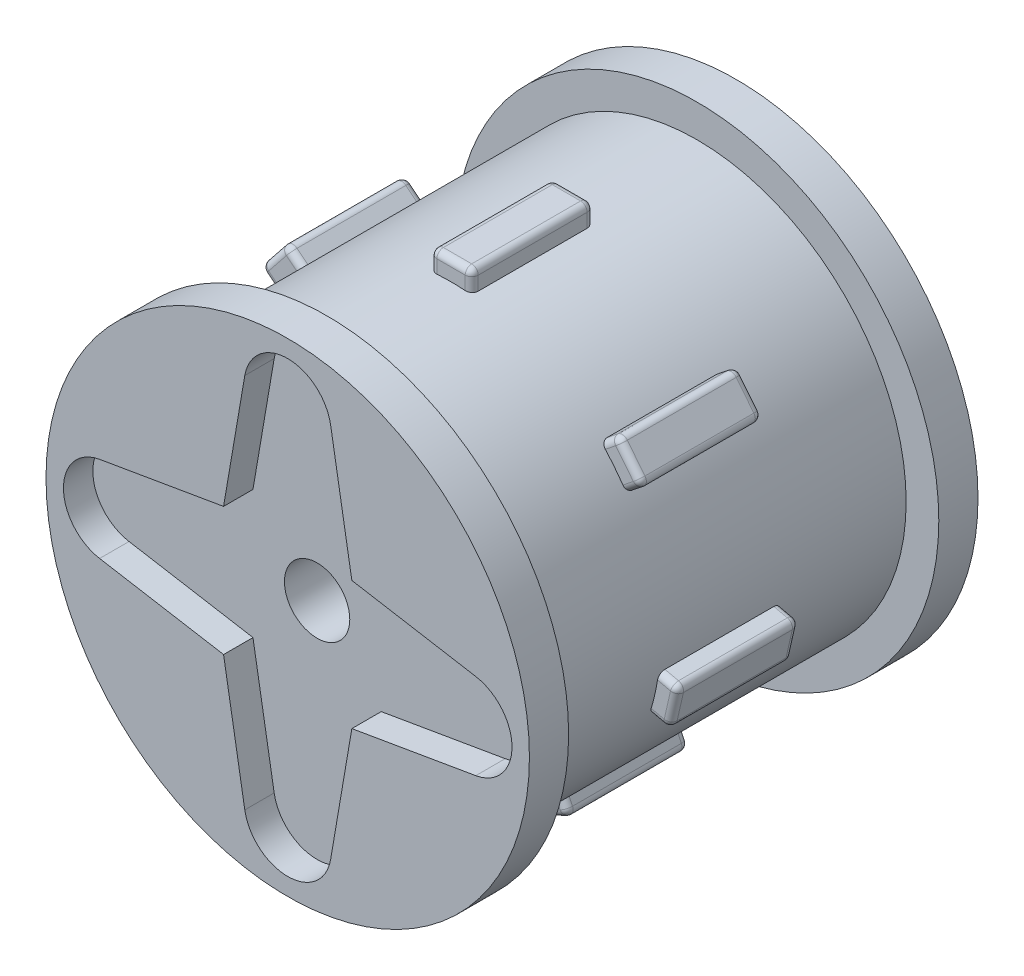
SolidWorks part; units mm, degrees
ref_plane "Ebene vorne" through (0, 0, 0) normal (0, 0, 1) x (1, 0, 0)
ref_plane "Ebene oben" through (0, 0, 0) normal (0, 1, 0) x (1, 0, 0)
ref_plane "Ebene rechts" through (0, 0, 0) normal (1, 0, 0) x (0, 0, -1)
sketch "Skizze1" plane through (0, 0, 0) normal (0, 0, 1) x (1, 0, 0)
  circle A0 centre (0, 0) radius 9.6
  dimension "D1" = 19.2
extrude "Aufsatz-Linear austragen1" add sketch "Skizze1" along normal blind 10.3 and the other way blind 10.3
ref_axis "Rotationsachse" through (0, 0, -10.3) along (0, 0, 1)
sketch "Skizze2" plane through (0, 0, 10.3) normal (0, 0, 1) x (1, 0, 0)
  circle A0 centre (0, 0) radius 11.1
  dimension "D1" = 22.2
extrude "Aufsatz-Linear austragen2" add sketch "Skizze2" against normal blind 1.8
sketch "Skizze3" plane through (0, 0, -10.3) normal (0, 0, -1) x (-1, 0, 0)
  circle A0 centre (0, 0) radius 11.1
  dimension "D1" = 22.2
extrude "Aufsatz-Linear austragen3" add sketch "Skizze3" against normal blind 1.8
sketch "Skizze4" plane through (0, 0, 10.3) normal (0, 0, 1) x (1, 0, 0)
  line L0 (-3.3513, 0.5735) -> (-1.9713, 8.6373)
  line L1 (3.3513, 0.5735) -> (1.9713, 8.6373)
  circle A0 centre (0, 0) radius 3.4
  circle A1 centre (0, 8.3) radius 2
  dimension "D1" = 6.8
  dimension "D3" = 4
  dimension "D2" = 8.3
extrude "Schnitt-Linear austragen1" cut sketch "Skizze4" against normal blind 1.35 contours A1 | A1 L0 A0 L1 | A0 region at (0, 4.7309, 10.3) region at (0, 0, 10.3) region at (0, 8.3, 10.3)
pattern_circular "Kreismuster1" count 4 over 360 about axis through (0, 0, -10.3) along (0, 0, 1) of "Schnitt-Linear austragen1"
sketch "Skizze8" plane through (0, 0, 0) normal (1, 0, 0) x (0, 0, -1)
  line L0 (10.3, 0) -> (10.3, 8)
  line L1 (10.3, -11.1) -> (10.3, 11.1) construction
  line L2 (10.3, 8) -> (8.5, 8)
  line L3 (8.5, 11.1) -> (8.5, -11.1) construction
  line L4 (8.5, 8) -> (-6.45, 3.5)
  line L6 (-6.45, 3.5) -> (-6.45, 0)
  line L7 (-6.45, 0) -> (10.3, 0)
  point P4 (-6.45, 0)
  dimension "D1" = 8
  dimension "D2" = 3.5
  dimension "D3" = 16.75
revolve "Schnitt-Rotation1" cut sketch "Skizze8" angle 360 about axis through (0, 0, -10.3) along (0, 0, 1)
sketch "Skizze9" plane through (0, 0, 8.95) normal (0, 0, 1) x (1, 0, 0)
  circle A0 centre (0, 0) radius 1.5
  dimension "D1" = 3
extrude "Schnitt-Linear austragen2" cut sketch "Skizze9" against normal through all
ref_plane "Schnittebene_Zaehne" through (0, 0, 0) normal (0, 0, -1) x (-1, 0, 0)
sketch "Skizze11" plane through (0, 0, 0) normal (0, 0, -1) x (-1, 0, 0)
  line L0 (0, 0) -> (0, 12.664) construction
  line L6 (-0.95, 8.71) -> (0.95, 8.71)
  line L7 (-0.95, 8.71) -> (-0.95, 10.49)
  line L8 (-0.95, 10.49) -> (0.95, 10.49)
  line L9 (0.95, 8.71) -> (0.95, 10.49)
  line L10 (-0.95, 8.71) -> (0.95, 10.49) construction
  line L11 (-0.95, 10.49) -> (0.95, 8.71) construction
  circle A1 centre (0, 0) radius 9.6 construction
  point P3 (0, 9.6)
  dimension "D1" = 0.89
  dimension "D2" = 1.9
extrude "Aufsatz-Linear austragen4" add sketch "Skizze11" along normal blind 2.8 and the other way blind 2.8
pattern_circular "Kreismuster2" count 7 over 360 about axis through (0, 0, -10.3) along (0, 0, 1) of "Aufsatz-Linear austragen4"
fillet "Verrundung1" radius 0.3 56 edges at (8.2014, 6.5404, 2.8) (7.6091, 7.2831, 0) (8.2014, 6.5404, -2.8) (8.7937, 5.7977, 0) (-8.4274, 5.5055, 2.8) (-7.2428, 6.991, 2.8) (-7.2428, 6.991, -2.8) (-8.4274, 5.5055, -2.8) (-9.5588, -3.1562, -2.8) (-9.9816, -1.3038, -2.8) (-9.5588, -3.1562, 2.8) (-9.9816, -1.3038, 2.8) (-5.2041, -8.6168, -2.8) (-3.4922, -9.4412, -2.8) (-3.4922, -9.4412, 2.8) (-5.2041, -8.6168, 2.8) (5.2041, -8.6168, 2.8) (3.4922, -9.4412, 2.8) (3.4922, -9.4412, -2.8) (5.2041, -8.6168, -2.8) (9.5588, -3.1562, 2.8) (9.5588, -3.1562, -2.8) (9.9816, -1.3038, 2.8) (9.9816, -1.3038, -2.8) (8.4274, 5.5055, 2.8) (8.4274, 5.5055, -2.8) (7.2428, 6.991, -2.8) (7.2428, 6.991, 2.8) (0.95, 10.0214, 2.8) (0.95, 10.0214, -2.8) (-0.95, 10.0214, -2.8) (-0.95, 10.0214, 2.8) (10.4384, -1.4081, 0) (10.227, -2.3342, 2.8) (10.227, -2.3342, -2.8) (10.0156, -3.2604, 0) (4.5514, -9.4512, 2.8) (4.5514, -9.4512, -2.8) (5.4074, -9.039, 0) (3.6955, -9.8634, 0) (-4.5514, -9.4512, 2.8) (-4.5514, -9.4512, -2.8) (-5.4074, -9.039, 0) (-3.6955, -9.8634, 0) (-10.227, -2.3342, 2.8) (-10.227, -2.3342, -2.8) (-10.0156, -3.2604, 0) (-10.4384, -1.4081, 0) (-8.2014, 6.5404, -2.8) (-8.2014, 6.5404, 2.8) (-8.7937, 5.7977, 0) (-7.6091, 7.2831, 0) (0, 10.49, -2.8) (0, 10.49, 2.8) (0.95, 10.49, 0) (-0.95, 10.49, 0)
